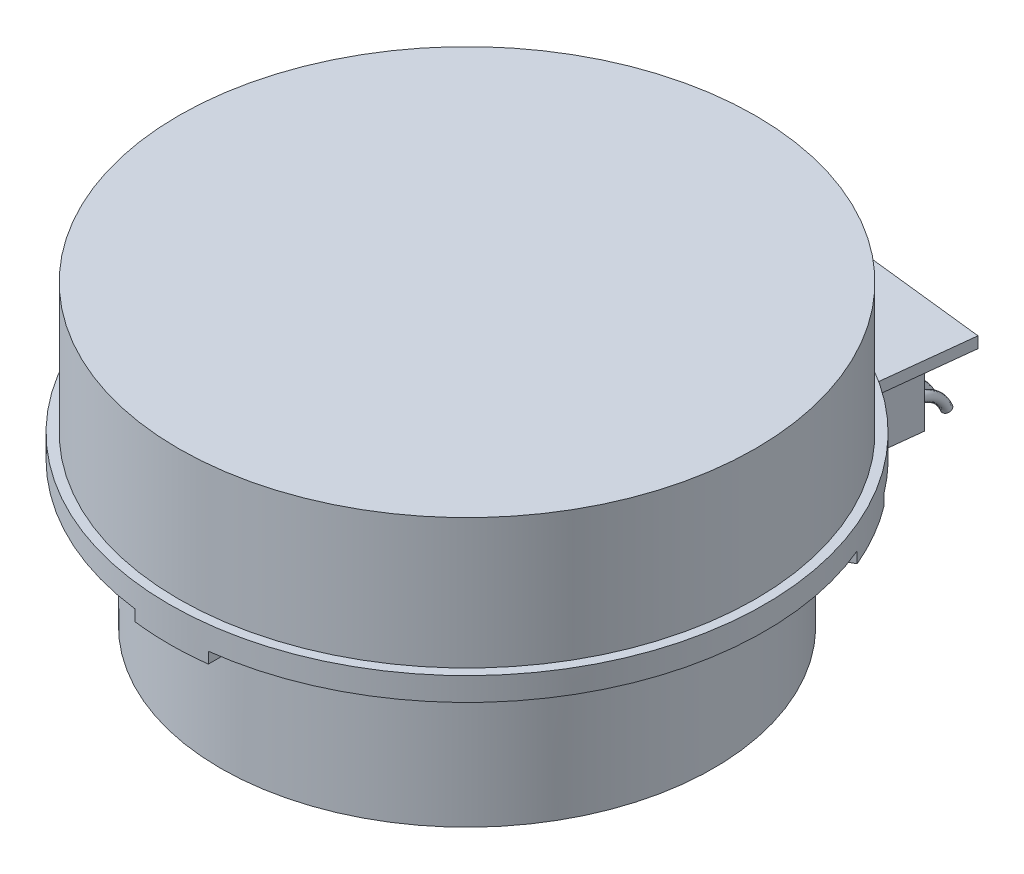
SolidWorks part; units mm, degrees
material "AISI 1020"
ref_plane "Plan de face" through (0, 0, 0) normal (0, 0, 1) x (1, 0, 0)
ref_plane "Plan de dessus" through (0, 0, 0) normal (0, 1, 0) x (1, 0, 0)
ref_plane "Plan de droite" through (0, 0, 0) normal (1, 0, 0) x (0, 0, -1)
sketch "Esquisse2" plane through (0, 0, 0) normal (0, 0, 1) x (1, 0, 0)
  line L0 (0, 0) -> (31, 0)
  line L1 (31, 0) -> (31, -14)
  line L2 (31, -14) -> (32, -14)
  line L3 (32, -14) -> (32, -16.5)
  line L4 (32, -16.5) -> (26.5, -16.5)
  line L5 (26.5, -16.5) -> (26.5, -32)
  line L6 (26.5, -32) -> (16, -32)
  line L7 (16, -32) -> (16, -36.5)
  line L8 (16, -36.5) -> (0, -36.5)
  line L9 (0, 27.034) -> (0, -56.9701) construction
  line L10 (0, 0) -> (0, -36.5)
  dimension "D1" = 31
  dimension "D2" = 14
  dimension "D3" = 2.5
  dimension "D4" = 32
  dimension "D5" = 26.5
  dimension "D6" = 16
  dimension "D7" = 4.5
  dimension "D8" = 15.5
revolve "Révolution2" add sketch "Esquisse2" angle 360 about L9
sketch "Esquisse3" plane through (0, -16.5, 0) normal (0, -1, 0) x (1, 0, 0)
  line L0 (-3.95, 26.204) -> (-3.95, 31.7553)
  line L1 (3.95, 31.7553) -> (3.95, 26.204)
  line L2 (0, 0) -> (0, 28.9) construction
  line L3 (24.6683, -9.6812) -> (29.4759, -12.4568)
  line L4 (25.5259, -19.2984) -> (20.7183, -16.5228)
  line L5 (-20.7183, -16.5228) -> (-25.5259, -19.2984)
  line L6 (-29.4759, -12.4568) -> (-24.6683, -9.6812)
  line L7 (-8.762, -25.0095) -> (-6.9055, -41.5309)
  line L8 (-6.9055, -41.5309) -> (15.9506, -38.9625)
  line L9 (15.9506, -38.9625) -> (14.0941, -22.4412)
  line L10 (0, 0) -> (4.5226, -40.2467) construction
  line L11 (-26.1938, 4.017) -> (-37.162, 3.6039)
  line L12 (-37.162, 3.6039) -> (-36.7856, -6.3891)
  line L13 (-36.7856, -6.3891) -> (-25.8174, -5.9759)
  line L14 (0, 0) -> (-36.9738, -1.3926) construction
  circle A2 centre (0, 0) radius 26.5 construction
  circle A3 centre (0, 0) radius 32 construction
  arc A4 (-3.95, 31.7553) -> (3.95, 31.7553) centre (0, 0) cw
  circle A5 centre (0, 28.9) radius 1
  arc A6 (-3.95, 26.204) -> (3.95, 26.204) centre (0, 0) cw
  arc A7 (29.4759, -12.4568) -> (25.5259, -19.2984) centre (0, 0) cw
  circle A8 centre (25.0281, -14.45) radius 1
  arc A9 (24.6683, -9.6812) -> (20.7183, -16.5228) centre (0, 0) cw
  arc A10 (-25.5259, -19.2984) -> (-29.4759, -12.4568) centre (0, 0) cw
  circle A11 centre (-25.0281, -14.45) radius 1
  arc A12 (-20.7183, -16.5228) -> (-24.6683, -9.6812) centre (0, 0) cw
  circle A13 centre (0, 0) radius 26.5 construction
  arc A14 (-8.762, -25.0095) -> (14.0941, -22.4412) centre (0, 0) ccw
  arc A15 (-25.8174, -5.9759) -> (-26.1938, 4.017) centre (0, 0) cw
  point P26 (0, 0)
  dimension "D4" = 2
  dimension "D7" = 40.5
  dimension "D1" = 7.9
  dimension "D2" = 3.95
  dimension "D3" = 28.9
  dimension "D6" = 23
  dimension "D8" = 29
  dimension "D9" = 10
  dimension "D10" = 37
  dimension "D11" = 9.5
  dimension "D5" = 3
extrude "Boss.-Extru.1" add sketch "Esquisse3" along normal blind 1.2
sketch "Esquisse4" plane through (0, -16.5, 0) normal (0, -1, 0) x (1, 0, 0)
  circle A0 centre (-25.1642, 14.414) radius 0.9
  dimension "D1" = 1.8
  dimension "D2" = 29
  dimension "D3" = 27.4
extrude "Boss.-Extru.2" add sketch "Esquisse4" along normal blind 2.3
sketch "Esquisse5" plane through (0, -17.7, 0) normal (0, -1, 0) x (1, 0, 0)
  line L0 (-6.9055, -41.5309) -> (15.9506, -38.9625) construction
  line L1 (-6.1351, -39.4317) -> (11.7523, -37.4217)
  line L2 (-6.1351, -39.4317) -> (-6.6934, -34.463)
  line L3 (-6.6934, -34.463) -> (11.194, -32.453)
  line L4 (11.7523, -37.4217) -> (11.194, -32.453)
  line L5 (-8.762, -25.0095) -> (-6.9055, -41.5309) construction
  dimension "D1" = 5
  dimension "D2" = 2
  dimension "D3" = 1
  dimension "D4" = 18
extrude "Boss.-Extru.3" add sketch "Esquisse5" along normal blind 9
sketch "Esquisse6" plane through (4.2992, 0, -38.2592) normal (0.1117, 0, -0.9937) x (-0.9937, 0, -0.1117)
  line L0 (10.5, -26.7) -> (10.5, -17.7) construction
  line L1 (10.5, -26.7) -> (-7.5, -26.7) construction
  circle A0 centre (8.5, -24.95) radius 0.5
  circle A1 centre (6.5, -24.95) radius 0.5
  circle A2 centre (4.5, -24.95) radius 0.5
  circle A3 centre (2.5, -24.95) radius 0.5
  circle A4 centre (0.5, -24.95) radius 0.5
  circle A5 centre (-1.5, -24.95) radius 0.5
  circle A6 centre (-3.5, -24.95) radius 0.5
  circle A7 centre (-5.5, -24.95) radius 0.5
  dimension "D2" = 1
  dimension "D3" = 2
  dimension "D4" = 1.75
  dimension "D1" = 8
sketch "Esquisse7" plane through (7.4531, 0, 0.8375) normal (0.9937, 0, 0.1117) x (0.1117, 0, -0.9937)
  line L0 (38.5, -25.45) -> (38.5, -24.45) construction
  spline S0 degree 2 poles (38.5, -24.95) (41.3679, -25.0875) (42.2362, -27.3139) knots 0 0 0 1 1 1
sweep "Balayage1" add profiles "Esquisse6" path "Esquisse7"
sketch "Esquisse8" plane through (0, -17.7, 0) normal (0, -1, 0) x (1, 0, 0)
  line L0 (-8.592, -28.7618) -> (6.9015, -29.2136)
  line L1 (6.9015, -29.2136) -> (7.0081, -25.5565)
  line L2 (-8.592, -28.7618) -> (-8.4853, -25.1048)
  line L3 (0, 0) -> (-0.8452, -28.9877) construction
  line L4 (-8.762, -25.0095) -> (-8.0934, -30.9596) construction
  arc A0 (-8.762, -25.0095) -> (14.0941, -22.4412) centre (0, 0) ccw construction
  arc A1 (-8.4853, -25.1048) -> (7.0081, -25.5565) centre (0, 0) ccw
  dimension "D1" = 15.5
  dimension "D2" = 29
  dimension "D3" = 0.25
extrude "Boss.-Extru.4" add sketch "Esquisse8" along normal blind 5.5
sketch "Esquisse9" plane through (0, -17.7, 0) normal (0, -1, 0) x (1, 0, 0)
  line L0 (11.7523, -37.4217) -> (11.194, -32.453) construction
  line L1 (-8.3396, -28.7692) -> (6.9015, -29.2136) construction
  circle A0 centre (9.1593, -27.7788) radius 1.5
  dimension "D1" = 1.5
  dimension "D2" = 1.5
extrude "Boss.-Extru.5" add sketch "Esquisse9" along normal blind 1.5
fillet "Congé1" radius 1.5 1 edges at (9.1593, -19.2, -29.2788)
